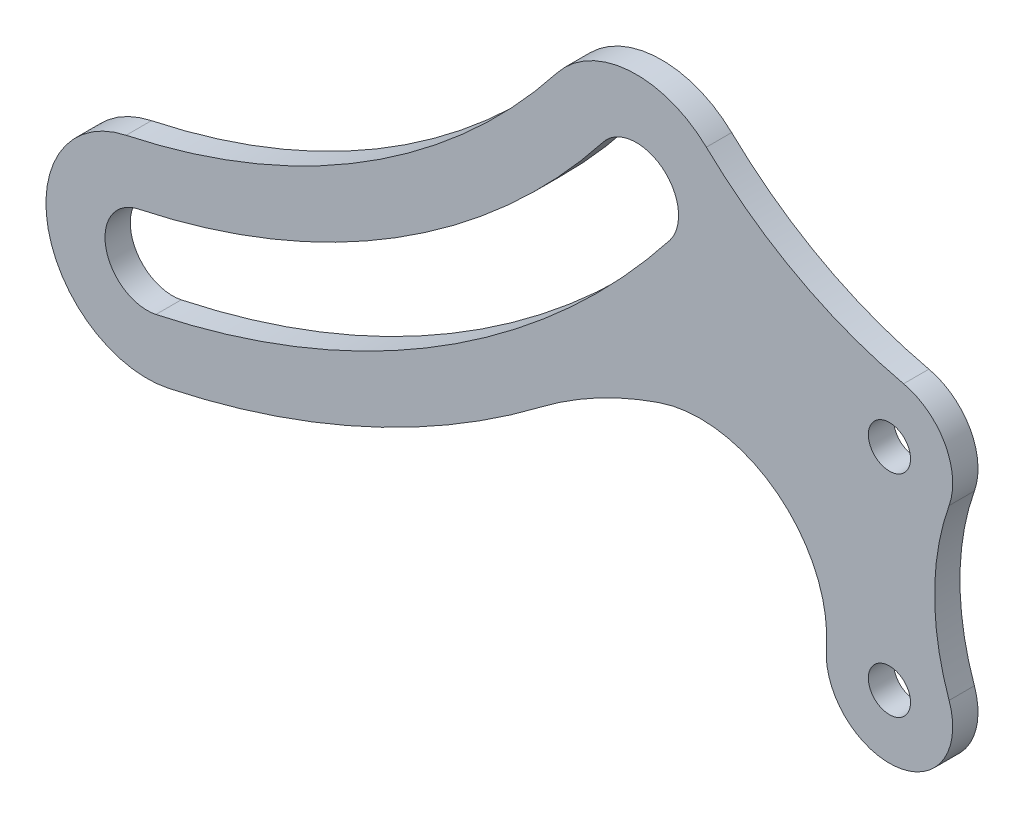
SolidWorks part; units mm, degrees
ref_plane "前视基准面" through (0, 0, 0) normal (0, 0, 1) x (1, 0, 0)
ref_plane "上视基准面" through (0, 0, 0) normal (0, 1, 0) x (1, 0, 0)
ref_plane "右视基准面" through (0, 0, 0) normal (1, 0, 0) x (0, 0, -1)
sketch "草图1" plane through (0, 0, 0) normal (0, 0, 1) x (1, 0, 0)
  line L1 (0, 0) -> (-20.7912, 97.8148) construction
  line L2 (0, -1.65) -> (0, 1.65) construction
  arc A4 (0, 0) -> (58, 36.2359) centre (-20.7912, 97.8148) ccw construction
  arc A18 (2.4949, -11.7378) -> (67.4549, 28.8465) centre (-20.7912, 97.8148) ccw
  arc A19 (-2.4949, 11.7378) -> (48.5451, 43.6254) centre (-20.7912, 97.8148) ccw
  arc A20 (2.4949, -11.7378) -> (-2.4949, 11.7378) centre (0, 0) cw
  arc A21 (67.4549, 28.8465) -> (48.5451, 43.6254) centre (58, 36.2359) ccw
  arc A22 (1.0396, -4.8907) -> (61.9396, 33.157) centre (-20.7912, 97.8148) ccw
  arc A23 (-1.0396, 4.8907) -> (54.0604, 39.3149) centre (-20.7912, 97.8148) ccw
  arc A24 (1.0396, -4.8907) -> (-1.0396, 4.8907) centre (0, 0) cw
  arc A25 (61.9396, 33.157) -> (54.0604, 39.3149) centre (58, 36.2359) ccw
  arc A26 (0, 0) -> (58, 36.2359) centre (-20.7912, 97.8148) ccw construction
  point P5 (-8.0402, 74.3879)
  dimension "D1" = 100
  dimension "D2" = 12
  dimension "D3" = 12
  dimension "D6" = 58
  dimension "D4" = 5
  dimension "D7" = 12
  dimension "D5" = 5
extrude "凸台-拉伸1" add sketch "草图1" along normal blind 3 contours A18 A21 A19 A20 A25 A22 A24 A23 region at (-10.7425, -2.2834, 0)
sketch "草图2" plane through (0, 0, 0) normal (0, 0, 1) x (1, 0, 0)
  line L0 (1.65, 0) -> (-1.65, 0) construction
  circle A1 centre (100.8493, 81.0459) radius 50
  circle A3 centre (76.8968, -31.4178) radius 50
  arc A6 (67.4549, 28.8465) -> (48.5451, 43.6254) centre (58, 36.2359) ccw construction
  circle A9 centre (88, 25) radius 7.5
  arc A25 (2.4949, -11.7378) -> (67.4549, 28.8465) centre (-20.7912, 97.8148) ccw
  arc A41 (67.4549, 28.8465) -> (48.5451, 43.6254) centre (58, 36.2359) ccw
  arc A43 (-2.4949, 11.7378) -> (48.5451, 43.6254) centre (-20.7912, 97.8148) ccw
  arc A45 (-2.4949, 11.7378) -> (2.4949, -11.7378) centre (0, 0) ccw
  arc A47 (2.4949, -11.7378) -> (67.4549, 28.8465) centre (-20.7912, 97.8148) ccw
  arc A48 (67.4549, 28.8465) -> (48.5451, 43.6254) centre (58, 36.2359) ccw
  arc A49 (-2.4949, 11.7378) -> (48.5451, 43.6254) centre (-20.7912, 97.8148) ccw
  arc A50 (-2.4949, 11.7378) -> (2.4949, -11.7378) centre (0, 0) ccw
  point P9 (72.6015, 9.2026)
  point P12 (0, 0)
  dimension "D1" = 15
  dimension "D2" = 100
  dimension "D4" = 0
  dimension "D5" = 25
  dimension "D3" = 100
  dimension "D6" = 30
extrude "凸台-拉伸2" add sketch "草图2" along normal blind 3 contours A9 | A9 region at (72.1833, 26.2949, 0) region at (88, 25, 0)
sketch "草图3" plane through (0, 0, 3) normal (0, 0, 1) x (1, 0, 0)
  arc A0 (86.5518, 17.6412) -> (89.676, 32.3103) centre (88, 25) ccw construction
  circle A1 centre (88, 25) radius 2.5
  dimension "D1" = 5
extrude "切除-拉伸1" cut sketch "草图3" against normal blind 3 contours A1
sketch "草图4" plane through (0, 0, 0) normal (0, 0, 1) x (1, 0, 0)
  line L0 (0, 0) -> (88, 0) construction
  line L1 (88, 0) -> (88, 25) construction
  circle A0 centre (88, 0) radius 7.5
  circle A1 centre (123.3553, 12.5) radius 30
  circle A3 centre (65.5641, 1.6967) radius 15
  arc A11 (66.2934, 44.9088) -> (48.5451, 43.6254) centre (58, 36.2359) ccw
  arc A12 (-2.4949, 11.7378) -> (48.5451, 43.6254) centre (-20.7912, 97.8148) ccw
  arc A13 (-2.4949, 11.7378) -> (2.4949, -11.7378) centre (0, 0) ccw
  arc A14 (2.4949, -11.7378) -> (46.7462, 8.4688) centre (-20.7912, 97.8148) ccw
  arc A15 (66.2934, 44.9088) -> (89.676, 32.3103) centre (100.8493, 81.0459) ccw
  arc A18 (66.2934, 44.9088) -> (48.5451, 43.6254) centre (58, 36.2359) ccw
  arc A19 (-2.4949, 11.7378) -> (48.5451, 43.6254) centre (-20.7912, 97.8148) ccw
  arc A20 (-2.4949, 11.7378) -> (2.4949, -11.7378) centre (0, 0) ccw
  arc A21 (2.4949, -11.7378) -> (46.7462, 8.4688) centre (-20.7912, 97.8148) ccw
  arc A26 (66.2934, 44.9088) -> (89.676, 32.3103) centre (100.8493, 81.0459) ccw
  arc A29 (86.5518, 17.6412) -> (46.7462, 8.4688) centre (76.8968, -31.4178) ccw
  arc A31 (86.5518, 17.6412) -> (46.7462, 8.4688) centre (76.8968, -31.4178) ccw
  arc A32 (86.5518, 17.6412) -> (89.676, 32.3103) centre (88, 25) ccw
  arc A33 (86.5518, 17.6412) -> (89.676, 32.3103) centre (88, 25) ccw
  point P3 (88, 25)
  point P8 (0, 0)
  point P10 (59.4841, -9.2383)
  point P12 (57.9196, -4.3253)
  point P13 (58.1014, -5.1673)
  point P15 (57.697, -2.9711)
  point P21 (117.1102, 5.3928)
  dimension "D1" = 15
  dimension "D2" = 60
  dimension "D4" = 30
  dimension "D3" = 0
extrude "凸台-拉伸3" add sketch "草图4" along normal blind 3 contours A3 L0 A0 A1 A33 A31 A21 | A0 | L0 A3 A0 region at (88, 0, 0) region at (83.5301, 12.9555, 0)
sketch "草图5" plane through (0, 0, 3) normal (0, 0, 1) x (1, 0, 0)
  circle A0 centre (88, 0) radius 2.5
  dimension "D1" = 5
extrude "切除-拉伸2" cut sketch "草图5" against normal through all
